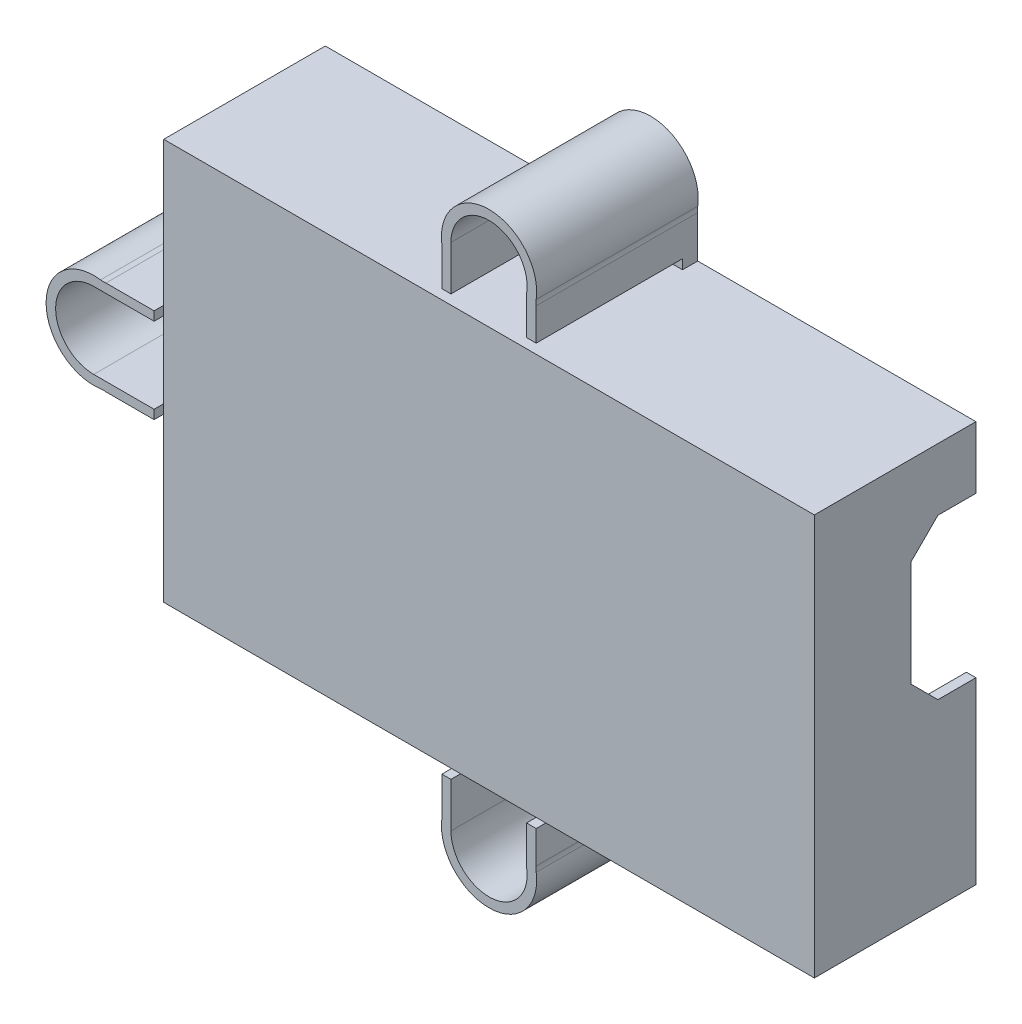
SolidWorks part; units mm, degrees
ref_plane "Front Plane" through (0, 0, 0) normal (0, 0, 1) x (1, 0, 0)
ref_plane "Top Plane" through (0, 0, 0) normal (0, 1, 0) x (1, 0, 0)
ref_plane "Right Plane" through (0, 0, 0) normal (1, 0, 0) x (0, 0, -1)
sketch "Sketch1" plane through (0, 0, 0) normal (0, 0, 1) x (1, 0, 0)
  line L0 (-16.375, 9.825) -> (16.375, -9.825) construction
  line L1 (-16.375, -9.825) -> (-16.575, -9.825) construction
  line L2 (16.575, 10.025) -> (-16.575, 10.025)
  line L3 (16.575, 10.025) -> (16.575, -10.025)
  line L4 (-16.375, 9.825) -> (-16.375, -9.825)
  line L5 (-16.375, -9.825) -> (16.375, -9.825)
  line L6 (16.375, -9.825) -> (16.375, 9.825)
  line L7 (16.375, 9.825) -> (-16.375, 9.825)
  line L8 (-16.375, 9.825) -> (-16.375, -9.825)
  line L9 (-16.375, -9.825) -> (16.375, -9.825)
  line L10 (16.375, -9.825) -> (16.375, 9.825)
  line L11 (16.375, 9.825) -> (-16.375, 9.825)
  line L12 (16.575, -10.025) -> (-16.575, -10.025)
  line L13 (-16.575, 10.025) -> (-16.575, -10.025)
  line L14 (16.575, 10.025) -> (-16.575, -10.025) construction
  line L15 (-13.9701, -11.875) -> (-3.4641, -11.875)
  line L18 (3.4641, -11.875) -> (13.9701, -11.875)
  line L19 (14.8161, -12.3418) -> (24.6724, -27.981)
  line L20 (31.4404, -23.7156) -> (19.404, -4.6171)
  line L21 (19.25, -4.084) -> (19.25, 4.084)
  line L22 (19.404, 4.6171) -> (31.4404, 23.7156)
  line L23 (24.6724, 27.981) -> (14.8161, 12.3418)
  line L24 (13.9701, 11.875) -> (3.4641, 11.875)
  line L25 (-3.4641, 11.875) -> (-13.9701, 11.875)
  line L26 (-14.8161, 12.3418) -> (-24.6724, 27.981)
  line L27 (-31.4404, 23.7156) -> (-19.404, 4.6171)
  line L28 (-19.25, 4.084) -> (-19.25, 3.4641)
  line L29 (-19.25, -3.4641) -> (-19.25, -4.084)
  line L30 (-19.404, -4.6171) -> (-31.4404, -23.7156)
  line L31 (-24.6724, -27.981) -> (-14.8161, -12.3418)
  line L32 (-13.9701, -11.875) -> (-3.4641, -11.875)
  line L33 (3.4641, -11.875) -> (13.9701, -11.875)
  line L34 (14.8161, -12.3418) -> (24.6724, -27.981)
  line L35 (31.4404, -23.7156) -> (19.404, -4.6171)
  line L36 (19.25, -4.084) -> (19.25, 4.084)
  line L37 (19.404, 4.6171) -> (31.4404, 23.7156)
  line L38 (24.6724, 27.981) -> (14.8161, 12.3418)
  line L39 (13.9701, 11.875) -> (3.4641, 11.875)
  line L40 (-3.4641, 11.875) -> (-13.9701, 11.875)
  line L41 (-14.8161, 12.3418) -> (-24.6724, 27.981)
  line L42 (-31.4404, 23.7156) -> (-19.404, 4.6171)
  line L43 (-19.25, 4.084) -> (-19.25, 3.4641)
  line L44 (-19.25, -3.4641) -> (-19.25, -4.084)
  line L45 (-19.404, -4.6171) -> (-31.4404, -23.7156)
  line L46 (-24.6724, -27.981) -> (-14.8161, -12.3418)
  line L47 (16.575, -10.025) -> (-16.575, 10.025) construction
  line L48 (-16.375, -9.825) -> (-16.375, -10.025) construction
  line L49 (-16.575, -10.025) -> (-17.075, -10.025) construction
  line L50 (17.075, 10.525) -> (-17.075, 10.525)
  line L51 (17.075, 10.525) -> (17.075, -10.525)
  line L52 (17.075, -10.525) -> (-17.075, -10.525)
  line L53 (-17.075, 10.525) -> (-17.075, -10.525)
  line L54 (17.075, 10.525) -> (-17.075, -10.525) construction
  line L55 (17.075, -10.525) -> (-17.075, 10.525) construction
  line L56 (-16.575, -10.025) -> (-16.575, -10.525) construction
  line L57 (-20.3929, -2.4744) -> (-17.075, -2.4744)
  line L58 (-20.3929, 2.4744) -> (-17.075, 2.4744)
  line L59 (-2.4744, -13.0179) -> (-2.4744, -10.525)
  line L60 (2.4744, -13.0179) -> (2.4744, -10.525)
  line L61 (-2.4744, 13.0179) -> (-2.4744, 10.525)
  line L62 (2.4744, 13.0179) -> (2.4744, 10.525)
  circle A0 centre (0, -13.375) radius 1.25
  circle A1 centre (-20.75, 0) radius 1.25
  circle A2 centre (0, 13.375) radius 1.25
  arc A32 (-2.4744, -13.0179) -> (-3.4641, -11.875) centre (-3.4641, -12.875) ccw
  arc A33 (-2.4744, -13.0179) -> (2.4744, -13.0179) centre (0, -13.375) ccw
  arc A34 (3.4641, -11.875) -> (2.4744, -13.0179) centre (3.4641, -12.875) ccw
  arc A35 (14.8161, -12.3418) -> (13.9701, -11.875) centre (13.9701, -12.875) ccw
  arc A36 (24.7505, -28.8963) -> (24.6724, -27.981) centre (23.8264, -28.5142) ccw
  arc A37 (24.7505, -28.8963) -> (32.2325, -24.1809) centre (31.8198, -31.8198) ccw
  arc A38 (31.4404, -23.7156) -> (32.2325, -24.1809) centre (32.2864, -23.1824) ccw
  arc A39 (19.25, -4.084) -> (19.404, -4.6171) centre (20.25, -4.084) ccw
  arc A40 (19.404, 4.6171) -> (19.25, 4.084) centre (20.25, 4.084) ccw
  arc A41 (32.2325, 24.1809) -> (31.4404, 23.7156) centre (32.2864, 23.1824) ccw
  arc A42 (32.2325, 24.1809) -> (24.7505, 28.8963) centre (31.8198, 31.8198) ccw
  arc A43 (24.6724, 27.981) -> (24.7505, 28.8963) centre (23.8264, 28.5142) ccw
  arc A44 (13.9701, 11.875) -> (14.8161, 12.3418) centre (13.9701, 12.875) ccw
  arc A45 (2.4744, 13.0179) -> (3.4641, 11.875) centre (3.4641, 12.875) ccw
  arc A46 (2.4744, 13.0179) -> (-2.4744, 13.0179) centre (0, 13.375) ccw
  arc A47 (-3.4641, 11.875) -> (-2.4744, 13.0179) centre (-3.4641, 12.875) ccw
  arc A48 (-14.8161, 12.3418) -> (-13.9701, 11.875) centre (-13.9701, 12.875) ccw
  arc A49 (-24.7505, 28.8963) -> (-24.6724, 27.981) centre (-23.8264, 28.5142) ccw
  arc A50 (-24.7505, 28.8963) -> (-32.2325, 24.1809) centre (-31.8198, 31.8198) ccw
  arc A51 (-31.4404, 23.7156) -> (-32.2325, 24.1809) centre (-32.2864, 23.1824) ccw
  arc A52 (-19.25, 4.084) -> (-19.404, 4.6171) centre (-20.25, 4.084) ccw
  arc A53 (-20.3929, 2.4744) -> (-19.25, 3.4641) centre (-20.25, 3.4641) ccw
  arc A54 (-20.3929, 2.4744) -> (-20.3929, -2.4744) centre (-20.75, 0) ccw
  arc A55 (-19.25, -3.4641) -> (-20.3929, -2.4744) centre (-20.25, -3.4641) ccw
  arc A56 (-19.404, -4.6171) -> (-19.25, -4.084) centre (-20.25, -4.084) ccw
  arc A57 (-32.2325, -24.1809) -> (-31.4404, -23.7156) centre (-32.2864, -23.1824) ccw
  arc A58 (-32.2325, -24.1809) -> (-24.7505, -28.8963) centre (-31.8198, -31.8198) ccw
  arc A59 (-24.6724, -27.981) -> (-24.7505, -28.8963) centre (-23.8264, -28.5142) ccw
  arc A60 (-13.9701, -11.875) -> (-14.8161, -12.3418) centre (-13.9701, -12.875) ccw
  arc A61 (-2.4744, -13.0179) -> (-3.4641, -11.875) centre (-3.4641, -12.875) ccw
  arc A62 (-2.4744, -13.0179) -> (2.4744, -13.0179) centre (0, -13.375) ccw
  arc A63 (3.4641, -11.875) -> (2.4744, -13.0179) centre (3.4641, -12.875) ccw
  arc A64 (14.8161, -12.3418) -> (13.9701, -11.875) centre (13.9701, -12.875) ccw
  arc A65 (24.7505, -28.8963) -> (24.6724, -27.981) centre (23.8264, -28.5142) ccw
  arc A66 (24.7505, -28.8963) -> (32.2325, -24.1809) centre (31.8198, -31.8198) ccw
  arc A67 (31.4404, -23.7156) -> (32.2325, -24.1809) centre (32.2864, -23.1824) ccw
  arc A68 (19.25, -4.084) -> (19.404, -4.6171) centre (20.25, -4.084) ccw
  arc A69 (19.404, 4.6171) -> (19.25, 4.084) centre (20.25, 4.084) ccw
  arc A70 (32.2325, 24.1809) -> (31.4404, 23.7156) centre (32.2864, 23.1824) ccw
  arc A71 (32.2325, 24.1809) -> (24.7505, 28.8963) centre (31.8198, 31.8198) ccw
  arc A72 (24.6724, 27.981) -> (24.7505, 28.8963) centre (23.8264, 28.5142) ccw
  arc A73 (13.9701, 11.875) -> (14.8161, 12.3418) centre (13.9701, 12.875) ccw
  arc A74 (2.4744, 13.0179) -> (3.4641, 11.875) centre (3.4641, 12.875) ccw
  arc A75 (2.4744, 13.0179) -> (-2.4744, 13.0179) centre (0, 13.375) ccw
  arc A76 (-3.4641, 11.875) -> (-2.4744, 13.0179) centre (-3.4641, 12.875) ccw
  arc A77 (-14.8161, 12.3418) -> (-13.9701, 11.875) centre (-13.9701, 12.875) ccw
  arc A78 (-24.7505, 28.8963) -> (-24.6724, 27.981) centre (-23.8264, 28.5142) ccw
  arc A79 (-24.7505, 28.8963) -> (-32.2325, 24.1809) centre (-31.8198, 31.8198) ccw
  arc A80 (-31.4404, 23.7156) -> (-32.2325, 24.1809) centre (-32.2864, 23.1824) ccw
  arc A81 (-19.25, 4.084) -> (-19.404, 4.6171) centre (-20.25, 4.084) ccw
  arc A82 (-20.3929, 2.4744) -> (-19.25, 3.4641) centre (-20.25, 3.4641) ccw
  arc A83 (-20.3929, 2.4744) -> (-20.3929, -2.4744) centre (-20.75, 0) ccw
  arc A84 (-19.25, -3.4641) -> (-20.3929, -2.4744) centre (-20.25, -3.4641) ccw
  arc A85 (-19.404, -4.6171) -> (-19.25, -4.084) centre (-20.25, -4.084) ccw
  arc A86 (-32.2325, -24.1809) -> (-31.4404, -23.7156) centre (-32.2864, -23.1824) ccw
  arc A87 (-32.2325, -24.1809) -> (-24.7505, -28.8963) centre (-31.8198, -31.8198) ccw
  arc A88 (-24.6724, -27.981) -> (-24.7505, -28.8963) centre (-23.8264, -28.5142) ccw
  arc A89 (-13.9701, -11.875) -> (-14.8161, -12.3418) centre (-13.9701, -12.875) ccw
  point P6 (0, 0)
  point P25 (0, 0)
  dimension "D4" = 0.5
  dimension "D5" = 2.5
  dimension "D1" = 0
  dimension "D2" = 0
  dimension "D3" = 0.2
extrude "Boss-Extrude1" add sketch "Sketch1" along normal offset from surface (7.98 mm away) 2.5 contours A84 L57 L53 L58 A82 A83 | L50 L53 L52 L51 L13 L2 L3 L12 | A63 L60 L52 L59 A61 A62 | A76 L61 L50 L62 A74 A75 region at (-2.4011, -11.6286, 0) region at (-9.7747, -10.1238, 0) region at (-18.5911, -2.3949, 0) region at (0, 10.5982, 0) offset beyond the face yes
sketch "Sketch2" plane through (0, 0, 7.98) normal (0, 0, 1) x (1, 0, 0)
  line L0 (-2.5, 10.525) -> (2.4744, 10.525)
  line L1 (-17.075, 2.5) -> (-17.075, -2.5)
  line L2 (-2.5, -10.525) -> (2.4744, -10.525)
  line L6 (-20.1071, -2.4744) -> (-17.075, -2.4744)
  line L7 (-20.1071, -2.4744) -> (-17.075, -2.4744)
  line L8 (-17.075, -2.4744) -> (-17.075, -10.525)
  line L9 (-17.075, -2.4744) -> (-17.075, -10.525)
  line L20 (-17.075, -10.525) -> (-2.4744, -10.525)
  line L21 (-17.075, -10.525) -> (-2.4744, -10.525)
  line L22 (-2.4744, -10.525) -> (-2.4744, -12.7321)
  line L23 (-2.4744, -10.525) -> (-2.4744, -12.7321)
  line L24 (2.4744, -12.7321) -> (2.4744, -10.525)
  line L25 (2.4744, -12.7321) -> (2.4744, -10.525)
  line L26 (2.4744, -10.525) -> (17.075, -10.525)
  line L27 (2.4744, -10.525) -> (17.075, -10.525)
  line L28 (17.075, -10.525) -> (17.075, 10.525)
  line L29 (17.075, -10.525) -> (17.075, 10.525)
  line L30 (17.075, 10.525) -> (2.4744, 10.525)
  line L31 (17.075, 10.525) -> (2.4744, 10.525)
  line L32 (2.4744, 10.525) -> (2.4744, 12.7321)
  line L33 (2.4744, 10.525) -> (2.4744, 12.7321)
  line L34 (-2.4744, 12.7321) -> (-2.4744, 10.525)
  line L35 (-2.4744, 12.7321) -> (-2.4744, 10.525)
  line L36 (-2.4744, 10.525) -> (-17.075, 10.525)
  line L37 (-2.4744, 10.525) -> (-17.075, 10.525)
  line L38 (-17.075, 10.525) -> (-17.075, 2.4744)
  line L39 (-17.075, 10.525) -> (-17.075, 2.4744)
  line L40 (-17.075, 2.4744) -> (-20.1071, 2.4744)
  line L41 (-17.075, 2.4744) -> (-20.1071, 2.4744)
  arc A9 (-20.1071, -2.4744) -> (-20.3929, -2.4744) centre (-20.25, -3.4641) ccw
  arc A10 (-20.1071, -2.4744) -> (-20.3929, -2.4744) centre (-20.25, -3.4641) ccw
  arc A11 (-2.4744, -13.0179) -> (-2.4744, -12.7321) centre (-3.4641, -12.875) ccw
  arc A12 (-2.4744, -13.0179) -> (-2.4744, -12.7321) centre (-3.4641, -12.875) ccw
  arc A13 (-2.4744, -13.0179) -> (2.4744, -13.0179) centre (0, -13.375) ccw
  arc A14 (-2.4744, -13.0179) -> (2.4744, -13.0179) centre (0, -13.375) ccw
  arc A15 (2.4744, -12.7321) -> (2.4744, -13.0179) centre (3.4641, -12.875) ccw
  arc A16 (2.4744, -12.7321) -> (2.4744, -13.0179) centre (3.4641, -12.875) ccw
  arc A17 (2.4744, 13.0179) -> (2.4744, 12.7321) centre (3.4641, 12.875) ccw
  arc A18 (2.4744, 13.0179) -> (2.4744, 12.7321) centre (3.4641, 12.875) ccw
  arc A19 (2.4744, 13.0179) -> (-2.4744, 13.0179) centre (0, 13.375) ccw
  arc A20 (2.4744, 13.0179) -> (-2.4744, 13.0179) centre (0, 13.375) ccw
  arc A21 (-2.4744, 12.7321) -> (-2.4744, 13.0179) centre (-3.4641, 12.875) ccw
  arc A22 (-2.4744, 12.7321) -> (-2.4744, 13.0179) centre (-3.4641, 12.875) ccw
  arc A23 (-20.3929, 2.4744) -> (-20.1071, 2.4744) centre (-20.25, 3.4641) ccw
  arc A24 (-20.3929, 2.4744) -> (-20.1071, 2.4744) centre (-20.25, 3.4641) ccw
  arc A25 (-20.3929, 2.4744) -> (-20.3929, -2.4744) centre (-20.75, 0) ccw
  arc A26 (-20.3929, 2.4744) -> (-20.3929, -2.4744) centre (-20.75, 0) ccw
  dimension "D1" = 0
extrude "Cut-Extrude1" cut sketch "Sketch2" against normal offset from surface (7.18 mm away) 0.8 contours L0 | L1 | L2 region at (0, 12.9704, 7.98) region at (-19.9289, 0, 7.98) region at (0, -12.9704, 7.98) up to face at (-5.364, 0, 0)
sketch "Sketch3" plane through (17.075, 0, 0) normal (1, 0, 0) x (0, 0, -1)
  line L0 (0, 10.525) -> (0, -10.525) construction
  line L1 (0, 7.265) -> (-3.395, 7.265)
  line L2 (0, 7.265) -> (0, -1.115)
  line L3 (0, -1.115) -> (-3.395, -1.115)
  line L4 (-3.395, 7.265) -> (-3.395, -1.115)
  line L6 (-1.3, 7.065) -> (-1.3, 7.265) construction
  line L7 (-1.3, -0.915) -> (-1.3, -1.115) construction
  line L8 (-3.195, 5.375) -> (-3.395, 5.375) construction
  dimension "D1" = 0.2
extrude "Cut-Extrude2" cut sketch "Sketch3" against normal up to next
chamfer "Chamfer1" distance 1.4 angle 45 2 edges at (16.825, -1.115, 3.395) (16.825, 7.265, 3.395)
sketch "Sketch4" plane through (0, 0, 7.98) normal (0, 0, 1) x (1, 0, 0)
  line L4 (-17.075, 10.525) -> (-17.075, -10.525)
  line L8 (-17.075, 10.525) -> (-17.075, -10.525)
  line L17 (-17.075, -10.525) -> (17.075, -10.525)
  line L18 (-17.075, -10.525) -> (17.075, -10.525)
  line L25 (17.075, -10.525) -> (17.075, 10.525)
  line L26 (17.075, -10.525) -> (17.075, 10.525)
  line L27 (17.075, 10.525) -> (-17.075, 10.525)
  line L28 (17.075, 10.525) -> (-17.075, 10.525)
  dimension "D1" = 0
extrude "Boss-Extrude2" add sketch "Sketch4" along normal blind 0.5
sketch "Sketch8" plane through (-17.075, 0, 0) normal (-1, 0, 0) x (0, 0, 1)
  line L1 (5.93, 3.385) -> (7.98, 3.385)
  line L2 (5.93, 3.385) -> (5.93, -3.385)
  line L3 (5.93, -3.385) -> (7.98, -3.385)
  line L4 (7.98, 3.385) -> (7.98, -3.385)
  line L7 (7.08, 3.385) -> (5.93, 3.385) construction
  line L8 (5.93, -3.385) -> (7.08, -3.385) construction
  line L9 (5.93, 3.385) -> (5.93, 2.4) construction
  line L10 (7.98, -3.985) -> (7.98, -2.4) construction
extrude "Cut-Extrude3" cut sketch "Sketch8" against normal up to next
sketch "Sketch9" plane through (0, 0, 7.98) normal (0, 0, -1) x (-1, 0, 0)
  line L1 (16.575, 2.4) -> (17.075, 2.4)
  line L2 (16.575, 2.4) -> (16.575, 3.385)
  line L3 (16.575, 3.385) -> (17.075, 3.385)
  line L4 (17.075, 2.4) -> (17.075, 3.385)
  line L5 (16.575, -2.4) -> (17.075, -2.4)
  line L6 (16.575, -2.4) -> (16.575, -3.385)
  line L7 (16.575, -3.385) -> (17.075, -3.385)
  line L8 (17.075, -2.4) -> (17.075, -3.385)
extrude "Boss-Extrude6" add sketch "Sketch9" along normal blind 0.8
sketch "Sketch5" plane through (0, 0, 0.8) normal (0, 0, 1) x (1, 0, 0)
  line L0 (-2, -13.375) -> (-2, -11.0315)
  line L1 (-17.075, 0) -> (17.075, 0) construction
  line L2 (17.075, -10.525) -> (17.075, 10.525) construction
  line L3 (-2.4744, 11.0315) -> (2.4744, 11.0315)
  line L4 (-2, 13.375) -> (-2, 11.0315)
  line L5 (1.9679, 13.0179) -> (1.9679, 11.0315)
  line L6 (-17.5815, 2.4744) -> (-17.5815, -2.4744)
  line L7 (-17.075, 0) -> (-17.5815, 0) construction
  line L8 (-20.75, 2) -> (-17.5815, 2)
  line L9 (-2.4744, 12.7321) -> (-2.4744, 10.525) construction
  line L10 (-2.4744, 10.525) -> (2.4744, 10.525) construction
  line L11 (2.4744, 10.525) -> (2.4744, 12.7321) construction
  line L12 (-20.1071, -2.4744) -> (-17.075, -2.4744) construction
  line L13 (-17.075, -2.4744) -> (-17.075, 2.4744) construction
  line L14 (-17.075, 2.4744) -> (-20.1071, 2.4744) construction
  line L15 (2.4744, -12.7321) -> (2.4744, -10.525) construction
  line L16 (2.4744, -10.525) -> (-2.4744, -10.525) construction
  line L17 (-2.4744, -10.525) -> (-2.4744, -12.7321) construction
  line L18 (-2.4744, 12.7321) -> (-2.4744, 10.525)
  line L19 (-2.4744, 10.525) -> (2.4744, 10.525)
  line L20 (2.4744, 10.525) -> (2.4744, 12.7321)
  line L21 (-20.1071, -2.4744) -> (-17.075, -2.4744)
  line L22 (-20.75, -2) -> (-17.5815, -2)
  line L23 (-17.075, -2.4744) -> (-17.075, 2.4744)
  line L24 (-17.075, 2.4744) -> (-20.1071, 2.4744)
  line L25 (2.4744, -12.7321) -> (2.4744, -10.525)
  line L26 (2.4744, -10.525) -> (-2.4744, -10.525)
  line L27 (-2.4744, -10.525) -> (-2.4744, -12.7321)
  line L28 (-2.4744, -11.0315) -> (2.4744, -11.0315)
  line L29 (0, -11.0315) -> (0, -10.525) construction
  line L30 (2.4744, -13.0179) -> (1.9679, -13.0179) construction
  line L31 (1.9679, -13.0179) -> (1.9679, -11.0315)
  circle A0 centre (0, 13.375) radius 2
  circle A1 centre (-20.75, 0) radius 2
  arc A3 (2.4744, 13.0179) -> (2.4744, 12.7321) centre (3.4641, 12.875) ccw construction
  arc A4 (2.4744, 13.0179) -> (-2.4744, 13.0179) centre (0, 13.375) ccw construction
  arc A5 (-2.4744, 12.7321) -> (-2.4744, 13.0179) centre (-3.4641, 12.875) ccw construction
  arc A6 (-20.3929, 2.4744) -> (-20.1071, 2.4744) centre (-20.25, 3.4641) ccw construction
  arc A7 (-20.3929, 2.4744) -> (-20.3929, -2.4744) centre (-20.75, 0) ccw construction
  arc A8 (-20.1071, -2.4744) -> (-20.3929, -2.4744) centre (-20.25, -3.4641) ccw construction
  arc A9 (-2.4744, -13.0179) -> (-2.4744, -12.7321) centre (-3.4641, -12.875) ccw construction
  arc A10 (-2.4744, -13.0179) -> (2.4744, -13.0179) centre (0, -13.375) ccw construction
  arc A11 (2.4744, -12.7321) -> (2.4744, -13.0179) centre (3.4641, -12.875) ccw construction
  arc A12 (2.4744, 13.0179) -> (2.4744, 12.7321) centre (3.4641, 12.875) ccw
  arc A13 (2.4744, 13.0179) -> (-2.4744, 13.0179) centre (0, 13.375) ccw
  arc A14 (-2.4744, 12.7321) -> (-2.4744, 13.0179) centre (-3.4641, 12.875) ccw
  arc A15 (-20.3929, 2.4744) -> (-20.1071, 2.4744) centre (-20.25, 3.4641) ccw
  arc A16 (-20.3929, 2.4744) -> (-20.3929, -2.4744) centre (-20.75, 0) ccw
  arc A17 (-20.1071, -2.4744) -> (-20.3929, -2.4744) centre (-20.25, -3.4641) ccw
  arc A18 (-2.4744, -13.0179) -> (-2.4744, -12.7321) centre (-3.4641, -12.875) ccw
  arc A19 (-2.4744, -13.0179) -> (2.4744, -13.0179) centre (0, -13.375) ccw
  arc A20 (2.4744, -12.7321) -> (2.4744, -13.0179) centre (3.4641, -12.875) ccw
  circle A21 centre (0, -13.375) radius 2
  dimension "D1" = 0.5
extrude "Boss-Extrude3" add sketch "Sketch5" along normal up to surface (7.68 mm away) contours A14 L18 L3 L4 A0 L5 L20 A12 A13 | A1 L8 L6 L22 | A21 L0 L28 L27 A18 A19 A20 L25 L31 region at (0, -15.4446, 0.8) region at (-2.4047, 11.8818, 0.8) region at (-17.6571, 2.2372, 0.8) up to face at (0, 0, 8.48)
sketch "Sketch11" plane through (0, 0, 7.98) normal (0, 0, -1) x (-1, 0, 0)
  line L24 (16.675, -4.085) -> (16.675, -2.3)
  line L25 (16.675, -2.3) -> (15.385, -2.3)
  line L26 (15.385, -2.3) -> (15.385, 2.3)
  line L27 (15.385, 2.3) -> (16.675, 2.3)
  line L28 (16.675, 2.3) -> (16.675, 4.085)
  line L29 (16.675, 4.085) -> (10.255, 4.085)
  line L30 (10.255, 4.085) -> (10.255, 2.4)
  line L31 (10.255, 2.4) -> (5.655, 2.4)
  line L32 (5.655, 2.4) -> (5.655, -2.4)
  line L33 (5.655, -2.4) -> (10.255, -2.4)
  line L34 (10.255, -2.4) -> (10.255, -4.085)
  line L35 (10.255, -4.085) -> (16.675, -4.085)
  line L36 (16.675, -4.085) -> (16.675, -2.3)
  line L37 (16.675, -2.3) -> (15.385, -2.3)
  line L38 (15.385, -2.3) -> (15.385, 2.3)
  line L39 (15.385, 2.3) -> (16.675, 2.3)
  line L40 (16.675, 2.3) -> (16.675, 4.085)
  line L41 (16.675, 4.085) -> (10.255, 4.085)
  line L42 (10.255, 4.085) -> (10.255, 2.4)
  line L43 (10.255, 2.4) -> (5.655, 2.4)
  line L44 (5.655, 2.4) -> (5.655, -2.4)
  line L45 (5.655, -2.4) -> (10.255, -2.4)
  line L46 (10.255, -2.4) -> (10.255, -4.085)
  line L47 (10.255, -4.085) -> (16.675, -4.085)
  line L48 (5.655, 1.9) -> (3.655, 1.9)
  line L49 (3.655, 0) -> (17.385, 0) construction
  line L50 (5.655, -1.9) -> (3.655, -1.9)
  line L51 (16.575, 6.085) -> (16.575, 4.085)
  line L53 (16.575, 10.025) -> (16.575, 2.4) construction
  line L54 (16.575, -6.085) -> (16.575, -4.085)
  line L55 (16.575, -2.4) -> (16.575, -10.025) construction
  line L60 (18.675, -6.085) -> (18.675, -0.3)
  line L61 (18.675, -0.3) -> (17.385, -0.3)
  line L62 (17.385, -0.3) -> (17.385, 0.3)
  line L63 (17.385, 0.3) -> (18.675, 0.3)
  line L64 (18.675, 0.3) -> (18.675, 6.085)
  line L65 (18.675, 6.085) -> (8.255, 6.085)
  line L66 (8.255, 6.085) -> (8.255, 4.4)
  line L67 (8.255, 4.4) -> (3.655, 4.4)
  line L68 (3.655, 4.4) -> (3.655, -4.4)
  line L69 (3.655, -4.4) -> (8.255, -4.4)
  line L70 (8.255, -4.4) -> (8.255, -6.085)
  line L71 (8.255, -6.085) -> (18.675, -6.085)
  line L72 (18.675, -6.085) -> (18.675, -0.3)
  line L73 (18.675, -0.3) -> (17.385, -0.3)
  line L74 (17.385, -0.3) -> (17.385, 0.3)
  line L75 (17.385, 0.3) -> (18.675, 0.3)
  line L76 (18.675, 0.3) -> (18.675, 6.085)
  line L77 (18.675, 6.085) -> (8.255, 6.085)
  line L78 (8.255, 6.085) -> (8.255, 4.4)
  line L79 (8.255, 4.4) -> (3.655, 4.4)
  line L80 (3.655, 4.4) -> (3.655, -4.4)
  line L81 (3.655, -4.4) -> (8.255, -4.4)
  line L82 (8.255, -4.4) -> (8.255, -6.085)
  line L83 (8.255, -6.085) -> (18.675, -6.085)
  line M27 (16.575, -10.025) -> (16.575, -2.4)
  line M31 (16.575, 2.4) -> (16.575, 10.025)
  dimension "D3" = 0.5
  dimension "D1" = 0.1
  dimension "D2" = 2.1
extrude "Boss-Extrude7" add sketch "Sketch11" along normal blind 2.5 contours L79 L80 L48 L44 L43 L42 L41 L77 L78 M31 | L82 L83 L47 L46 L45 L44 L50 L80 L81 M27 region at (-9.8383, -4.2692, 7.98) region at (-9.8383, 4.2692, 7.98)
sketch "Sketch12" plane through (0, 0, 7.98) normal (0, 0, -1) x (-1, 0, 0)
  line L0 (16.575, -6.085) -> (16.575, -10.025) construction
  line L1 (-3.0335, 0) -> (1.6631, 0) construction
  line L2 (16.575, 8.055) -> (14.605, 8.055)
  line L3 (16.575, 8.055) -> (16.575, 6.085)
  line L4 (16.575, 6.085) -> (14.605, 6.085)
  line L5 (16.575, -8.055) -> (14.605, -8.055)
  line L6 (16.575, -8.055) -> (16.575, -6.085)
  line L7 (16.575, -6.085) -> (14.605, -6.085)
  line L8 (14.605, -8.055) -> (14.605, -6.085)
  line L9 (8.255, -6.085) -> (16.575, -6.085) construction
  line L10 (14.605, 8.055) -> (14.605, 6.085)
  line L11 (-16.575, 10.025) -> (-16.575, -10.025) construction
  line L12 (-14.605, 2) -> (-16.575, 2)
  line L13 (-14.605, 2) -> (-14.605, -2)
  line L14 (-14.605, -2) -> (-16.575, -2)
  line L15 (-16.575, 2) -> (-16.575, -2)
  line L16 (-14.605, 2) -> (-16.575, -2) construction
  line L17 (-14.605, -2) -> (-16.575, 2) construction
  point P16 (-15.59, 0)
  dimension "D1" = 4
extrude "Boss-Extrude8" add sketch "Sketch12" along normal up to surface (3.95 mm away)
